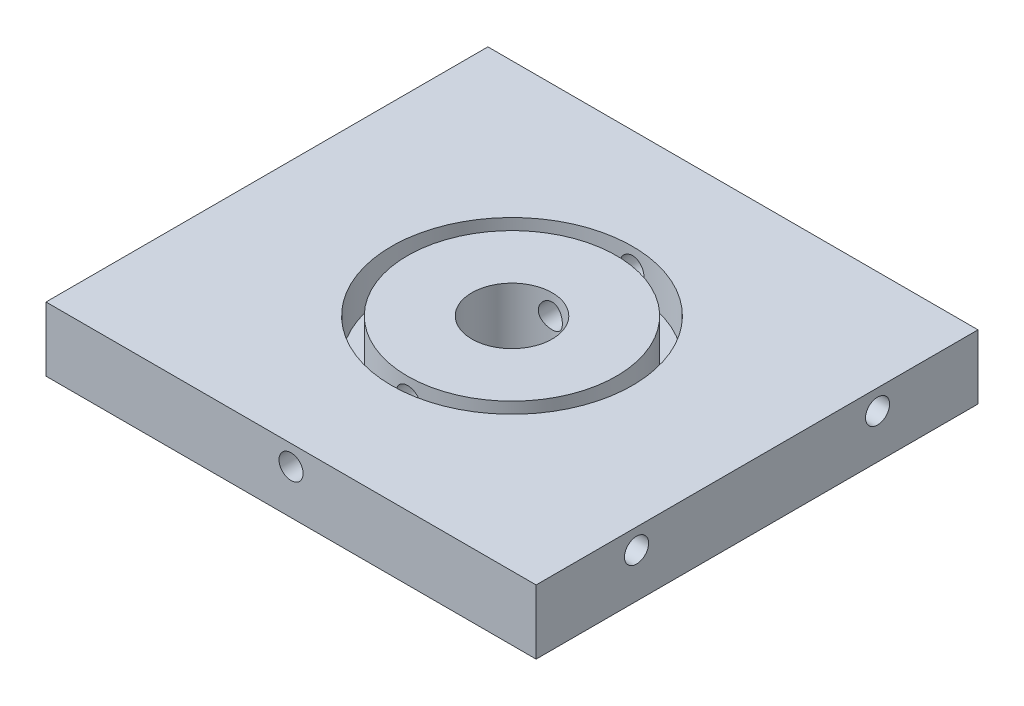
SolidWorks part; units mm, degrees
material "PLA"
ref_plane "Plan de face" through (0, 0, 0) normal (0, 0, 1) x (1, 0, 0)
ref_plane "Plan de dessus" through (0, 0, 0) normal (0, 1, 0) x (1, 0, 0)
ref_plane "Plan de droite" through (0, 0, 0) normal (1, 0, 0) x (0, 0, -1)
sketch "Esquisse1" plane through (0, 0, 0) normal (0, 0, 1) x (1, 0, 0)
  line L0 (-5.5, -49) -> (55.5, -49) construction
  line L5 (-5.5, -45) -> (55.5, -45)
  line L6 (-5.5, -45) -> (-5.5, -53)
  line L7 (-5.5, -53) -> (55.5, -53)
  line L8 (55.5, -45) -> (55.5, -53)
  line L9 (25, -45) -> (25, -53) construction
  dimension "D1" = 8
  dimension "D2" = 61
extrude "Boss.-Extru.1" add sketch "Esquisse1" along normal blind 55 contours L5 | L7 L8 L5 L6
sketch "Esquisse2" plane through (0, -45, 0) normal (0, 1, 0) x (-1, 0, 0)
  line L0 (5.5, 55) -> (-55.5, 55) construction
  line L7 (-55.5, 55) -> (-55.5, 0) construction
  circle A0 centre (-25, 27.5) radius 15
  circle A2 centre (-25, 27.5) radius 13
  dimension "D10" = 30.5
  dimension "D11" = 27.5
extrude "Enlèv. mat.-Extru.1" cut sketch "Esquisse2" against normal blind 5
sketch "Esquisse3" plane through (-5.5, 0, 0) normal (-1, 0, 0) x (0, 0, 1)
  line L0 (55, -53) -> (0, -53) construction
  line L1 (0, -45) -> (0, -53) construction
  line L2 (55, -45) -> (55, -53) construction
  circle A0 centre (12.5, -47.5) radius 1.5
  circle A1 centre (42.5, -47.5) radius 1.5
  dimension "D1" = 5.5
  dimension "D2" = 5.5
  dimension "D3" = 12.5
  dimension "D4" = 12.5
extrude "Enlèv. mat.-Extru.2" cut sketch "Esquisse3" against normal blind 10
sketch "Esquisse4" plane through (55.5, 0, 0) normal (1, 0, 0) x (0, 0, -1)
  line L0 (-55, -53) -> (0, -53) construction
  line L1 (-55, -45) -> (-55, -53) construction
  line L2 (0, -45) -> (0, -53) construction
  circle A0 centre (-42.5, -47.5) radius 1.5
  circle A1 centre (-12.5, -47.5) radius 1.5
  dimension "D1" = 5.5
  dimension "D2" = 5.5
  dimension "D3" = 12.5
  dimension "D4" = 12.5
extrude "Enlèv. mat.-Extru.3" cut sketch "Esquisse4" against normal blind 10
sketch "Esquisse5" plane through (0, 0, 0) normal (0, 0, -1) x (-1, 0, 0)
  line L0 (5.5, -45) -> (-55.5, -45) construction
  line L1 (-55.5, -45) -> (-55.5, -53) construction
  circle A0 centre (-25, -47.5) radius 1.5
  dimension "D1" = 2.5
  dimension "D2" = 30.5
extrude "Enlèv. mat.-Extru.4" cut sketch "Esquisse5" against normal through all
sketch "Esquisse6" plane through (0, -45, 0) normal (0, 1, 0) x (1, 0, 0)
  line L0 (-5.5, -55) -> (-5.5, 0) construction
  line L1 (-5.5, -55) -> (55.5, -55) construction
  circle A0 centre (25, -27.5) radius 5
  dimension "D1" = 30.5
  dimension "D2" = 27.5
extrude "Enlèv. mat.-Extru.5" cut sketch "Esquisse6" against normal through all contours A0
